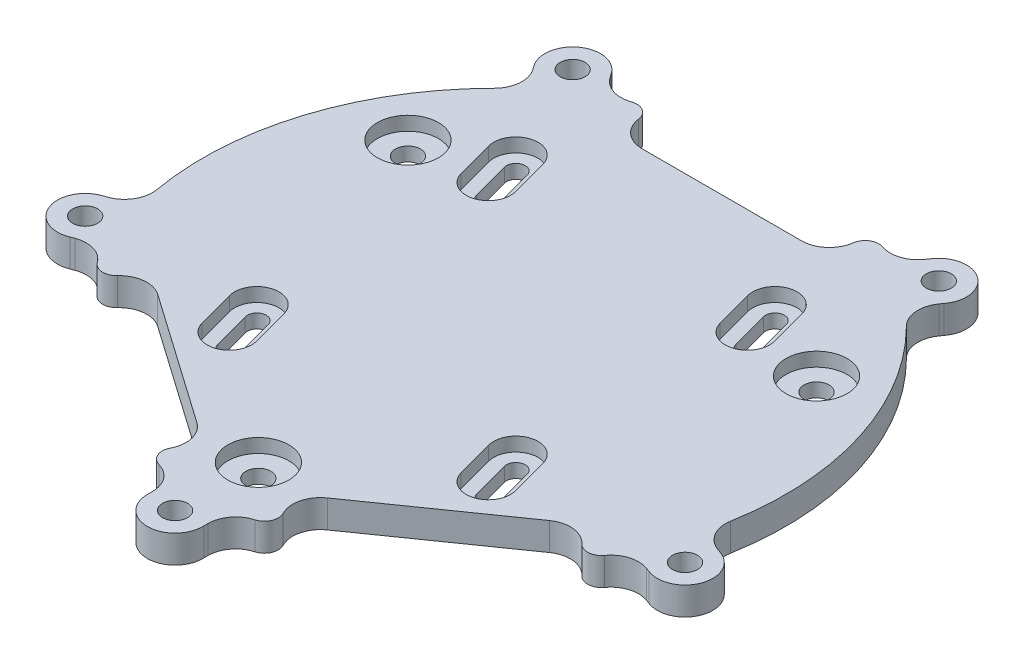
SolidWorks part; units mm, degrees
ref_plane "Plan de face" through (0, 0, 0) normal (0, 0, 1) x (1, 0, 0)
ref_plane "Plan de dessus" through (0, 0, 0) normal (0, 1, 0) x (1, 0, 0)
ref_plane "Plan de droite" through (0, 0, 0) normal (1, 0, 0) x (0, 0, -1)
sketch "Sketch1" plane through (0, 0, 0) normal (0, 1, 0) x (1, 0, 0)
  line L0 (0, 0) -> (0, 41) construction
  line L1 (0, 0) -> (-23.5166, -33.5852) construction
  line L2 (0, 0) -> (23.5166, -33.5852) construction
  line L3 (-39.3263, -22.5152) -> (-7.707, -44.6553)
  line L4 (7.707, -44.6553) -> (39.3263, -22.5152)
  line L5 (-19.3, 41) -> (19.3, 41)
  line L6 (-19.3, 41) -> (-19.3, 48.8238)
  line L8 (19.3, 41) -> (19.3, 48.8238)
  line L9 (7.707, -44.6553) -> (12.1945, -51.0641)
  line L11 (39.3263, -22.5152) -> (43.8138, -28.9241)
  line L12 (-7.707, -44.6553) -> (-12.1945, -51.0641)
  line L13 (-39.3263, -22.5152) -> (-43.8138, -28.9241)
  line L14 (0, 0) -> (0, -42.5) construction
  line L15 (0, 0) -> (-36.8061, 21.25) construction
  line L16 (0, 0) -> (36.8061, 21.25) construction
  arc A0 (-19.3, 48.8238) -> (-43.8138, -28.9241) centre (0, 0) ccw
  arc A1 (43.8138, -28.9241) -> (19.3, 48.8238) centre (0, 0) ccw
  circle A3 centre (-36.8061, 21.25) radius 2.25 construction
  circle A4 centre (36.8061, 21.25) radius 2.25 construction
  circle A6 centre (0, -42.5) radius 2.25 construction
  arc A7 (-12.1945, -51.0641) -> (12.1945, -51.0641) centre (0, 0) ccw
  circle A8 centre (-36.8061, 21.25) radius 5.5
  circle A9 centre (36.8061, 21.25) radius 5.5
  circle A10 centre (0, -42.5) radius 5.5
  point P25 (23.5166, -33.5852)
  point P26 (-23.5166, -33.5852)
  dimension "D1" = 105
  dimension "D5" = 35
  dimension "D6" = 38.6
  dimension "D10" = 4.5
  dimension "D4" = 11
  dimension "D9" = 42.5
  dimension "D2" = 35
  dimension "D3" = 41
  dimension "D7" = 120
  dimension "D8" = 120
extrude "Boss-Extrude1" add sketch "Sketch1" along normal blind 5 contours L4 A0 L5 L3 | A8 | A9 | A10 region at (0, 0, -1.6314) region at (-36.8061, 0, -21.25) region at (36.8061, 0, -21.25) region at (0, 0, 42.5)
sketch "Esquisse1" plane through (0, 5, 0) normal (0, 1, 0) x (1, 0, 0)
  line L0 (0, 0) -> (-23.3345, 23.3345) construction
  line L1 (0, 0) -> (0, 41) construction
  line L2 (-19.3, 41) -> (19.3, 41) construction
  line L3 (-24.758, 28.6471) -> (-22.9463, 21.8856) construction
  line L4 (-23.116, 29.0871) -> (-21.3042, 22.3256)
  line L5 (-26.4001, 28.2071) -> (-24.5884, 21.4456)
  line L6 (0, 0) -> (23.3345, 23.3345) construction
  line L7 (0, 0) -> (23.3345, -23.3345) construction
  line L8 (0, 0) -> (-23.3345, -23.3345) construction
  line L9 (23.7228, 21.8856) -> (21.911, 28.6471) construction
  line L10 (22.0807, 21.4456) -> (20.2689, 28.2071)
  line L11 (25.3648, 22.3256) -> (23.5531, 29.0871)
  line L12 (23.7228, -24.7834) -> (21.911, -18.0219) construction
  line L13 (22.0807, -25.2234) -> (20.2689, -18.4619)
  line L14 (25.3648, -24.3434) -> (23.5531, -17.5819)
  line L15 (-22.9463, -24.7834) -> (-24.758, -18.0219) construction
  line L16 (-24.5884, -25.2234) -> (-26.4001, -18.4619)
  line L17 (-21.3042, -24.3434) -> (-23.116, -17.5819)
  line L18 (0, 0) -> (-10.9859, 41) construction
  line L19 (-22.9463, 21.8856) -> (-24.758, 28.6471) construction
  line L20 (-26.81, 20.8504) -> (-28.6217, 27.6118)
  line L21 (-19.0826, 22.9209) -> (-20.8943, 29.6824)
  line L22 (23.7228, 21.8856) -> (21.911, 28.6471) construction
  line L23 (19.859, 20.8504) -> (18.0473, 27.6118)
  line L24 (27.5865, 22.9209) -> (25.7747, 29.6824)
  line L25 (23.7228, -24.7834) -> (21.911, -18.0219) construction
  line L26 (19.859, -25.8187) -> (18.0473, -19.0572)
  line L27 (27.5865, -23.7481) -> (25.7747, -16.9867)
  line L28 (-22.9463, -24.7834) -> (-24.758, -18.0219) construction
  line L29 (-26.81, -25.8187) -> (-28.6217, -19.0572)
  line L30 (-19.0826, -23.7481) -> (-20.8943, -16.9867)
  arc A0 (-23.116, 29.0871) -> (-26.4001, 28.2071) centre (-24.758, 28.6471) ccw
  arc A1 (-24.5884, 21.4456) -> (-21.3042, 22.3256) centre (-22.9463, 21.8856) ccw
  arc A2 (22.0807, 21.4456) -> (25.3648, 22.3256) centre (23.7228, 21.8856) ccw
  arc A3 (23.5531, 29.0871) -> (20.2689, 28.2071) centre (21.911, 28.6471) ccw
  arc A4 (22.0807, -25.2234) -> (25.3648, -24.3434) centre (23.7228, -24.7834) ccw
  arc A5 (23.5531, -17.5819) -> (20.2689, -18.4619) centre (21.911, -18.0219) ccw
  arc A6 (-24.5884, -25.2234) -> (-21.3042, -24.3434) centre (-22.9463, -24.7834) ccw
  arc A7 (-23.116, -17.5819) -> (-26.4001, -18.4619) centre (-24.758, -18.0219) ccw
  arc A8 (-26.81, 20.8504) -> (-19.0826, 22.9209) centre (-22.9463, 21.8856) ccw
  arc A9 (-20.8943, 29.6824) -> (-28.6217, 27.6118) centre (-24.758, 28.6471) ccw
  arc A10 (19.859, 20.8504) -> (27.5865, 22.9209) centre (23.7228, 21.8856) ccw
  arc A11 (25.7747, 29.6824) -> (18.0473, 27.6118) centre (21.911, 28.6471) ccw
  arc A12 (19.859, -25.8187) -> (27.5865, -23.7481) centre (23.7228, -24.7834) ccw
  arc A13 (25.7747, -16.9867) -> (18.0473, -19.0572) centre (21.911, -18.0219) ccw
  arc A14 (-26.81, -25.8187) -> (-19.0826, -23.7481) centre (-22.9463, -24.7834) ccw
  arc A15 (-20.8943, -16.9867) -> (-28.6217, -19.0572) centre (-24.758, -18.0219) ccw
  point P8 (-23.8522, 25.2664)
  point P18 (22.8169, 25.2664)
  point P25 (22.8169, -21.4027)
  point P30 (-23.8522, -21.4027)
  point P40 (-23.8522, 25.2664)
  point P45 (22.8169, 25.2664)
  point P52 (22.8169, -21.4027)
  point P59 (-23.8522, -21.4027)
  dimension "D5" = 1.7
  dimension "D9" = 4
  dimension "D1" = 1.5
  dimension "D2" = 5.5
  dimension "D3" = 15
  dimension "D4" = 33
  dimension "D6" = 45
  dimension "D7" = 1.5
  dimension "D8" = 30
extrude "Enlèv. mat.-Extru.1" cut sketch "Esquisse1" against normal up to next contours L5 A1 L4 A0 | L11 A3 L10 A2 | L14 A5 L13 A4 | L17 A7 L16 A6 region at (-23.8522, 5, -25.2664) region at (22.8169, 5, -25.2664) region at (22.8169, 5, 21.4027) region at (-23.8522, 5, 21.4027)
extrude "Enlèv. mat.-Extru.2" cut sketch "Esquisse1<3>" against normal blind 2.5
sketch "Esquisse1<3>" plane through (0, 5, 0) normal (0, 1, 0) x (1, 0, 0) same geometry as "Esquisse1"
extrude "Enlèv. mat.-Extru.3" cut sketch "Sketch1<3>" against normal blind 2.5 from surface contours A8 | A9 | A10 region at (-36.8061, 0, -21.25) region at (36.8061, 0, -21.25) region at (0, 0, 42.5) starting at face at (-23.8522, 5, 21.4027)
sketch "Sketch1<3>" plane through (0, 0, 0) normal (0, 1, 0) x (1, 0, 0) same geometry as "Sketch1"
sketch "Esquisse4" plane through (0, 5, 0) normal (0, 1, 0) x (1, 0, 0)
  point P0 (0, -42.5)
  point P3 (36.8061, 21.25)
  point P6 (-36.8061, 21.25)
hole_wizard "M4 Clearance Hole1" positions "Esquisse4" profile "Esquisse3" hole size "M4" standard "ANSI Metric" end condition up to next
sketch "Esquisse3" plane through (0, 5, 42.5) normal (1, 0, 0) x (0, 0, 1)
  line L0 (0, 0) -> (0, 5)
  line L1 (0, 5) -> (2.25, 5)
  line L2 (2.25, 5) -> (2.25, 0)
  line L5 (2.25, 0) -> (0, 0)
  line L11 (0, -6.35) -> (0, 107.95) construction
  dimension "Thru Hole Dia." = 4.5
  dimension "Thru Hole Depth" = 5
fillet "Congé1" radius 2.5 6 edges at (19.3, 2.5, -48.8238) (-19.3, 2.5, -48.8238) (-43.8138, 2.5, 28.9241) (43.8138, 2.5, 28.9241) (12.1945, 2.5, 51.0641) (-12.1945, 2.5, 51.0641)
sketch "Esquisse5" plane through (0, 5, 0) normal (0, 1, 0) x (1, 0, 0)
  line L0 (0, 0) -> (0, -57.5) construction
  line L1 (0, 0) -> (54.0323, -19.6662) construction
  line L2 (0, 0) -> (32.9806, 47.1012) construction
  line L3 (0, 0) -> (-32.9806, 47.1012) construction
  line L4 (0, 0) -> (-54.0323, -19.6662) construction
  line L5 (-52.1196, -24.2858) -> (-47.4016, -22.5686)
  line L6 (-55.5365, -14.8978) -> (-50.8185, -13.1806)
  line L7 (-36.9478, 44.058) -> (-34.068, 39.9452)
  line L8 (-28.7641, 49.7883) -> (-25.8843, 45.6755)
  line L9 (36.9478, 44.058) -> (34.068, 39.9452)
  line L10 (28.7641, 49.7883) -> (25.8843, 45.6755)
  line L11 (52.1196, -24.2858) -> (47.4016, -22.5686)
  line L12 (55.5365, -14.8978) -> (50.8185, -13.1806)
  line L13 (4.9953, -57.2826) -> (4.9953, -52.2618)
  line L14 (-4.9953, -57.2826) -> (-4.9953, -52.2618)
  arc A0 (-4.9953, -57.2826) -> (-52.1196, -24.2858) centre (0, 0) ccw construction
  arc A1 (52.1196, -24.2858) -> (55.5365, -14.8978) centre (54.0323, -19.6662) ccw
  arc A2 (-4.9953, -57.2826) -> (4.9953, -57.2826) centre (0, -57.5) ccw
  arc A3 (-55.5365, -14.8978) -> (-52.1196, -24.2858) centre (-54.0323, -19.6662) ccw
  arc A4 (-28.7641, 49.7883) -> (-36.9478, 44.058) centre (-32.9806, 47.1012) ccw
  arc A5 (36.9478, 44.058) -> (28.7641, 49.7883) centre (32.9806, 47.1012) ccw
  arc A6 (-8.3495, -51.8318) -> (8.3495, -51.8318) centre (0, 0) ccw construction
  arc A7 (-22.89, 47.2472) -> (-45.8503, -25.5735) centre (0, 0) ccw construction
  arc A8 (45.8503, -25.5735) -> (22.89, 47.2472) centre (0, 0) ccw construction
  arc A9 (-8.3495, -51.8318) -> (8.3495, -51.8318) centre (0, 0) ccw construction
  arc A10 (47.4016, -22.5686) -> (50.8185, -13.1806) centre (0, 0) ccw
  arc A11 (34.068, 39.9452) -> (25.8843, 45.6755) centre (0, 0) ccw
  arc A12 (-25.8843, 45.6755) -> (-34.068, 39.9452) centre (0, 0) ccw
  arc A13 (-50.8185, -13.1806) -> (-47.4016, -22.5686) centre (0, 0) ccw
  arc A14 (-4.9953, -52.2618) -> (4.9953, -52.2618) centre (0, 0) ccw
  dimension "D1" = 70
  dimension "D5" = 10
  dimension "D2" = 70
  dimension "D3" = 75
  dimension "D4" = 75
extrude "Boss.-Extru.1" add sketch "Esquisse5" against normal up to surface (5 mm away) up to face at (0, 0, 44.75)
sketch "Esquisse8" plane through (0, 5, 0) normal (0, 1, 0) x (1, 0, 0)
  point P0 (0, -57.5)
  point P3 (54.0323, -19.6662)
  point P6 (32.9806, 47.1012)
  point P9 (-32.9806, 47.1012)
  point P12 (-54.0323, -19.6662)
hole_wizard "M4 Clearance Hole2" positions "Esquisse8" profile "Esquisse7" hole size "M4" standard "ANSI Metric" end condition up to next
sketch "Esquisse7" plane through (0, 5, 57.5) normal (1, 0, 0) x (0, 0, 1)
  line L0 (0, 0) -> (0, 5)
  line L1 (0, 5) -> (2.25, 5)
  line L2 (2.25, 5) -> (2.25, 0)
  line L5 (2.25, 0) -> (0, 0)
  line L11 (0, -6.35) -> (0, 107.95) construction
  dimension "Thru Hole Dia." = 4.5
  dimension "Thru Hole Depth" = 5
fillet "Congé2" radius 5 16 edges at (47.4016, 2.5, 22.5686) (50.8185, 2.5, 13.1806) (34.068, 2.5, -39.9452) (-34.068, 2.5, -39.9452) (-50.8185, 2.5, 13.1806) (-47.4016, 2.5, 22.5686) (4.9953, 2.5, 52.2618) (-4.9953, 2.5, 52.2618) (25.8843, 2.5, -45.6755) (-25.8843, 2.5, -45.6755) (-7.707, 2.5, 44.6553) (-39.3263, 2.5, 22.5152) (-19.3, 2.5, -41) (19.3, 2.5, -41) (39.3263, 2.5, 22.5152) (7.707, 2.5, 44.6553)
